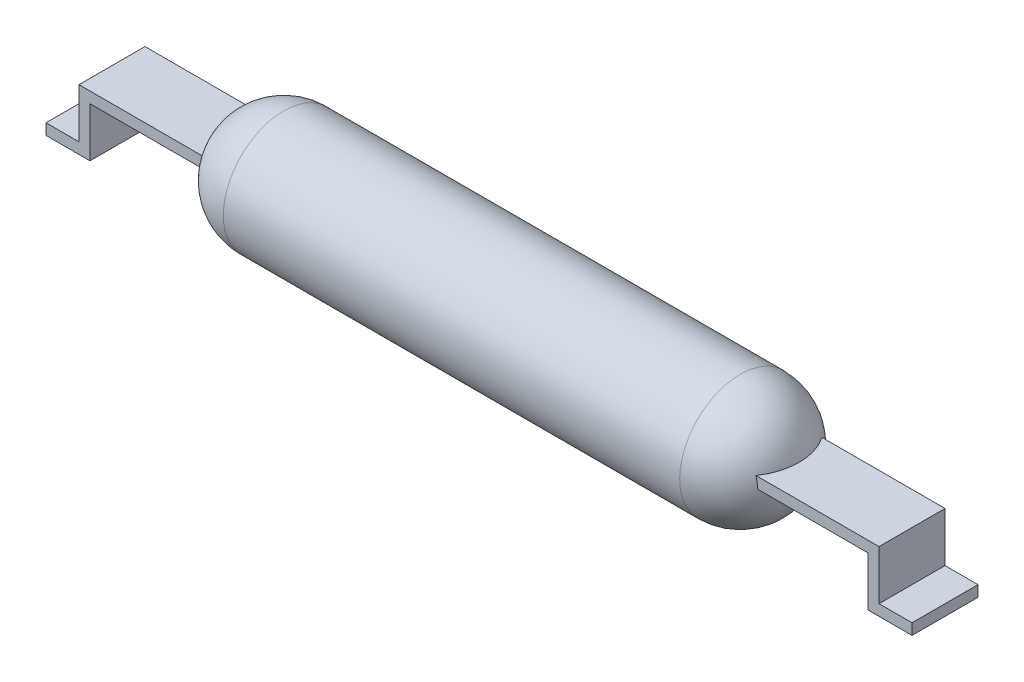
SolidWorks part; units mm, degrees
ref_plane "Plan de face" through (0, 0, 0) normal (0, 0, 1) x (1, 0, 0)
ref_plane "Plan de dessus" through (0, 0, 0) normal (0, 1, 0) x (1, 0, 0)
ref_plane "Plan de droite" through (0, 0, 0) normal (1, 0, 0) x (0, 0, -1)
sketch "Esquisse1" plane through (0, 0, 0) normal (0, 1, 0) x (1, 0, 0)
  line L0 (-0.525, 0) -> (0.525, 0) construction
  line L2 (0.525, 0) -> (0.525, 0.11)
  line L3 (0.525, 0.11) -> (-0.525, 0.11)
  line L4 (-0.525, 0) -> (-0.525, 0.11)
  line L5 (-0.525, 0) -> (0.525, 0)
  point P0 (0, 0)
  point P10 (0, 0)
  dimension "D1" = 1.05
  dimension "D2" = 0.11
revolve "Révolution2" add sketch "Esquisse1" angle 360 about L0
fillet "Congé2" radius 0.11 2 edges at (0.525, 0, 0.11) (-0.525, 0, 0.11)
sketch "Esquisse2" plane through (0, 0, 0) normal (0, 0, 1) x (1, 0, 0)
  line L0 (-0.7075, -0.085) -> (-0.7875, -0.085)
  line L1 (-0.7875, -0.085) -> (-0.7875, -0.065)
  line L2 (-0.7875, -0.065) -> (-0.7275, -0.065)
  line L3 (-0.7275, -0.065) -> (-0.7275, 0.025)
  line L4 (-0.7275, 0.025) -> (-0.415, 0.025)
  line L5 (-0.415, 0.025) -> (-0.415, 0.005)
  line L6 (-0.415, 0.005) -> (-0.7075, 0.005)
  line L7 (-0.7075, 0.005) -> (-0.7075, -0.085)
  line L8 (0.415, 0.11) -> (-0.415, 0.11) construction
  line L9 (0, -0.121) -> (0, 0.121) construction
  line L10 (0.415, 0.005) -> (0.7075, 0.005)
  line L11 (0.415, 0.025) -> (0.415, 0.005)
  line L12 (0.7275, 0.025) -> (0.415, 0.025)
  line L13 (0.7275, -0.065) -> (0.7275, 0.025)
  line L14 (0.7875, -0.065) -> (0.7275, -0.065)
  line L15 (0.7875, -0.085) -> (0.7875, -0.065)
  line L16 (0.7075, -0.085) -> (0.7875, -0.085)
  line L17 (0.7075, 0.005) -> (0.7075, -0.085)
  line L18 (-0.415, -0.11) -> (-0.415, 0.11) construction
  dimension "D1" = 0.08
  dimension "D2" = 0.11
  dimension "D3" = 0.02
  dimension "D4" = 0.195
  dimension "D5" = 0.02
  dimension "D6" = 0.02
  dimension "D7" = 1.575
extrude "Boss.-Extru.1" add sketch "Esquisse2" along normal blind 0.06 and the other way blind 0.06
